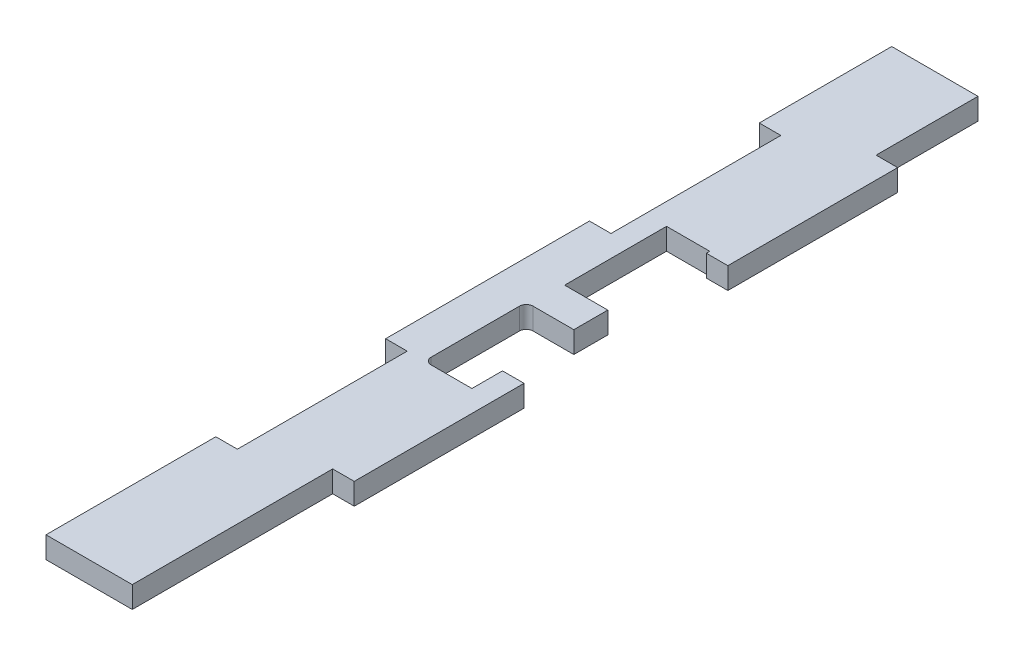
SolidWorks part; units mm, degrees
material "Balsa"
ref_plane "Front Plane" through (0, 0, 0) normal (0, 0, 1) x (1, 0, 0)
ref_plane "Top Plane" through (0, 0, 0) normal (0, 1, 0) x (1, 0, 0)
ref_plane "Right Plane" through (0, 0, 0) normal (1, 0, 0) x (0, 0, -1)
sketch "Sketch2" plane through (0, 0, 0) normal (0, 1, 0) x (1, 0, 0)
  line L13 (0, 0) -> (25.4, 0)
  line L14 (0, 0) -> (0, 249)
  line L15 (0, 249) -> (25.4, 249)
  line L16 (25.4, 0) -> (25.4, 59)
  line L17 (25.4, 59) -> (31.75, 59)
  line L19 (25.4, 109) -> (31.75, 109)
  line L20 (31.75, 59) -> (31.75, 109)
  line L21 (25.4, 169) -> (31.75, 169)
  line L22 (31.75, 169) -> (31.75, 219)
  line L23 (25.4, 219) -> (31.75, 219)
  line L25 (25.4, 219) -> (25.4, 249)
  line L26 (25.4, 109) -> (25.4, 169)
  dimension "D1" = 25.4
  dimension "D2" = 249
  dimension "D3" = 6.35
  dimension "D4" = 50
  dimension "D5" = 59
  dimension "D6" = 2
  dimension "D7" = 30
extrude "Boss-Extrude1" add sketch "Sketch2" along normal blind 6.35
sketch "Sketch3" plane through (0, 6.35, 0) normal (0, 1, 0) x (1, 0, 0)
  line L5 (25.4, 109) -> (25.4, 169) construction
  line L6 (25.4, 130) -> (11.4, 130)
  line L7 (25.4, 130) -> (25.4, 100)
  line L8 (25.4, 100) -> (11.4, 100)
  line L9 (11.4, 130) -> (11.4, 100)
  line L10 (0, 0) -> (25.4, 0) construction
  line L12 (25.4, 140) -> (12.7, 140)
  line L13 (25.4, 140) -> (25.4, 170)
  line L14 (25.4, 170) -> (12.7, 170)
  line L15 (12.7, 140) -> (12.7, 170)
  dimension "D4" = 30
  dimension "D1" = 100
  dimension "D2" = 14
  dimension "D3" = 30
  dimension "D5" = 12.7
  dimension "D6" = 10
extrude "Cut-Extrude1" cut sketch "Sketch3" against normal through all
fillet "Fillet1" radius 2 2 edges at (11.4, 3.175, -100) (11.4, 3.175, -130)
sketch "Sketch4" plane through (0, 6.35, 0) normal (0, 1, 0) x (1, 0, 0)
  line L0 (0, 249) -> (0, 0) construction
  line L1 (0, 50) -> (6.35, 50)
  line L2 (0, 50) -> (0, 100)
  line L3 (0, 100) -> (6.35, 100)
  line L4 (6.35, 50) -> (6.35, 100)
  line L5 (0, 0) -> (25.4, 0) construction
  line L6 (0, 160) -> (0, 210)
  line L7 (0, 160) -> (6.35, 160)
  line L8 (6.35, 160) -> (6.35, 210)
  line L9 (0, 210) -> (6.35, 210)
  line L10 (25.4, 249) -> (0, 249) construction
  dimension "D1" = 6.35
  dimension "D2" = 50
  dimension "D3" = 50
  dimension "D5" = 39
  dimension "D4" = 2
extrude "Cut-Extrude2" cut sketch "Sketch4" against normal through all
